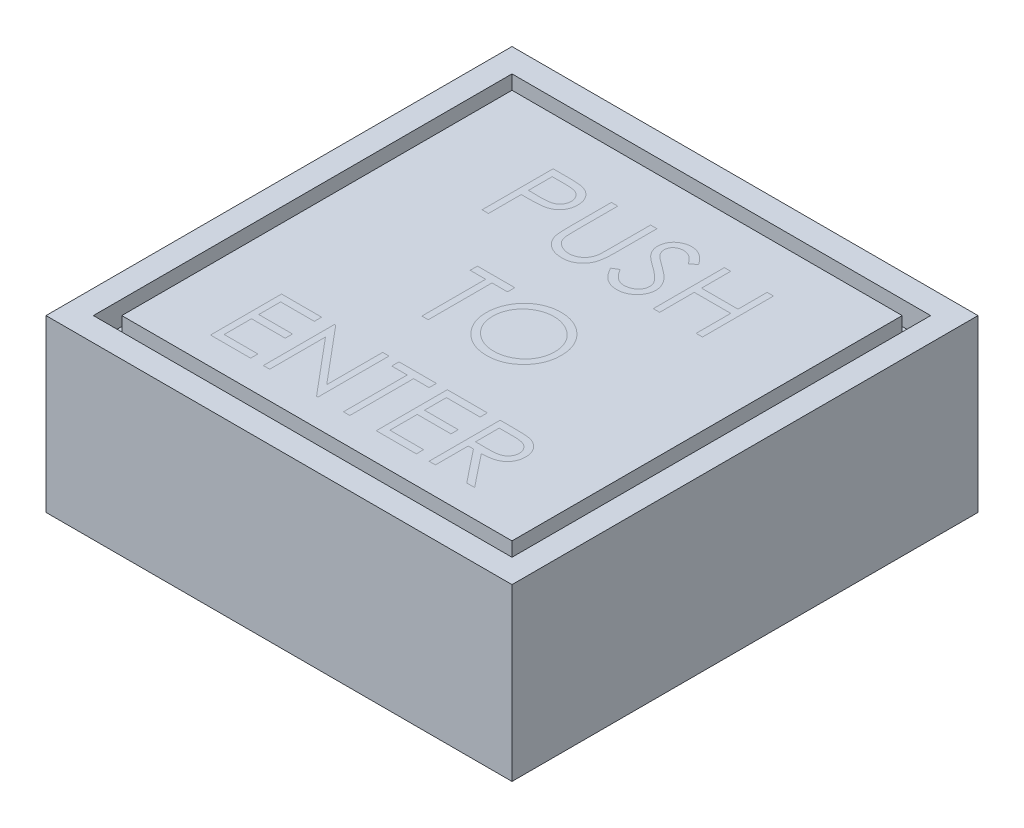
SolidWorks part; units mm, degrees
material "Stainless Steel (ferritic)"
ref_plane "Front Plane" through (0, 0, 0) normal (0, 0, 1) x (1, 0, 0)
ref_plane "Back of Button Plane" through (0, 0, 0) normal (0, 1, 0) x (1, 0, 0)
ref_plane "Right Plane" through (0, 0, 0) normal (1, 0, 0) x (0, 0, -1)
sketch "Sketch1" plane through (0, 0, 0) normal (0, 1, 0) x (1, 0, 0)
  line L1 (0, 0) -> (124.968, 0)
  line L2 (0, 0) -> (0, 124.968)
  line L3 (0, 124.968) -> (124.968, 124.968)
  line L4 (124.968, 0) -> (124.968, 124.968)
  dimension "D1" = 124.968
  dimension "D2" = 124.968
extrude "Boss-Extrude1" add sketch "Sketch1" along normal blind 45.72
sketch "Sketch4" plane through (0, 45.72, 0) normal (0, 1, 0) x (1, 0, 0)
  line L8 (6.35, 118.618) -> (6.35, 6.35)
  line L9 (6.35, 6.35) -> (118.618, 6.35)
  line L10 (118.618, 6.35) -> (118.618, 118.618)
  line L11 (118.618, 118.618) -> (6.35, 118.618)
  line L12 (6.35, 118.618) -> (6.35, 6.35)
  line L13 (6.35, 6.35) -> (118.618, 6.35)
  line L14 (118.618, 6.35) -> (118.618, 118.618)
  line L15 (118.618, 118.618) -> (6.35, 118.618)
  dimension "D1" = 6.35
extrude "Cut-Extrude1" cut sketch "Sketch4" against normal blind 6.35
sketch "Sketch6" plane through (0, 39.37, 0) normal (0, 1, 0) x (1, 0, 0)
  line L8 (114.808, 10.16) -> (114.808, 114.808)
  line L9 (10.16, 10.16) -> (114.808, 10.16)
  line L10 (10.16, 114.808) -> (10.16, 10.16)
  line L11 (114.808, 114.808) -> (10.16, 114.808)
  line L12 (114.808, 10.16) -> (114.808, 114.808)
  line L13 (10.16, 10.16) -> (114.808, 10.16)
  line L14 (10.16, 114.808) -> (10.16, 10.16)
  line L15 (114.808, 114.808) -> (10.16, 114.808)
  dimension "D1" = 3.81
extrude "Boss-Extrude2" add sketch "Sketch6" along normal blind 6.35
sketch "Sketch11" plane through (0, 45.72, 0) normal (0, 1, 0) x (1, 0, 0)
  text T0 " PUSH \r\n   TO\r\nENTER" font "Century Gothic" height in points 72
wrap "Wrap1" sketch "Sketch11" wrap type scribe source sketch "Sketch11" face at (62.484, 45.72, -62.484)
